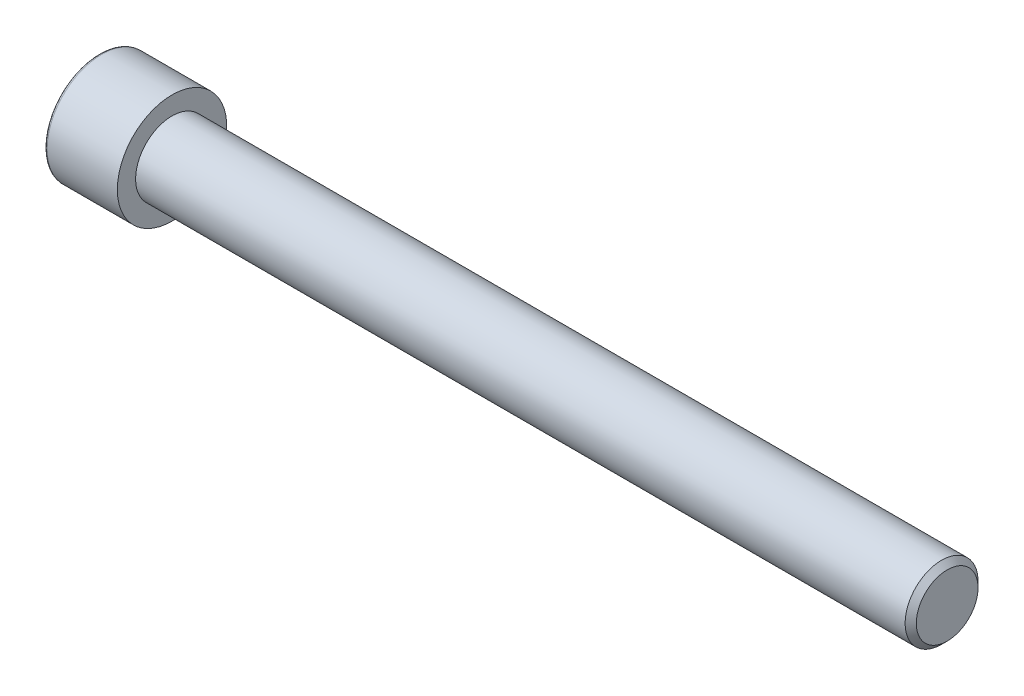
SolidWorks part; units mm, degrees
ref_plane "Płaszczyzna przednia" through (0, 0, 0) normal (0, 0, 1) x (1, 0, 0)
ref_plane "Płaszczyzna górna" through (0, 0, 0) normal (0, 1, 0) x (1, 0, 0)
ref_plane "Płaszczyzna prawa" through (0, 0, 0) normal (1, 0, 0) x (0, 0, -1)
sketch "Szkic1" plane through (0, 0, 0) normal (0, 0, 1) x (1, 0, 0)
  line L0 (0, 0) -> (0, 12)
  line L1 (0, 12) -> (16, 12)
  line L2 (16, 12) -> (16, 0)
  line L3 (16, 0) -> (0, 0)
  line L4 (16, 0) -> (0, 0) construction
revolve "Obrót1" add sketch "Szkic1" angle 360 about L4 reverse direction yes
sketch "Szkic2" plane through (0, 0, 0) normal (0, 0, 1) x (1, 0, 0)
  line L0 (0, 12) -> (0, 11.4)
  line L1 (0.6, 12) -> (0, 12)
  line L2 (16, 0) -> (0, 0) construction
  arc A0 (0, 11.4) -> (0.6, 12) centre (0.6, 11.4) cw
revolve "Wycięcie-obrót1" cut sketch "Szkic2" angle 360 about L2 reverse direction yes
sketch "Szkic3" plane through (0, 0, 0) normal (0, 0, 1) x (1, 0, 0)
  line L0 (16, 0) -> (16, 8)
  line L1 (16, 8) -> (184.773, 8)
  line L2 (184.773, 8) -> (186, 6.773)
  line L3 (186, 6.773) -> (186, 0)
  line L4 (186, 0) -> (16, 0)
  line L5 (186, 0) -> (16, 0) construction
revolve "Obrót2" add sketch "Szkic3" angle 360 about L5 reverse direction yes
cosmetic thread "Oznaczenie gwintu1" parameters "D1"=44, "D2"=13.546
sketch "Szkic4" plane through (0, 0, 0) normal (0, 0, 1) x (1, 0, 0)
  line L0 (0, 0) -> (0, 8.5)
  line L1 (0, 8.5) -> (8, 8.5)
  line L2 (8, 8.5) -> (12.9075, 0)
  line L3 (12.9075, 0) -> (0, 0)
  line L4 (12.9075, 0) -> (0, 0) construction
revolve "Wycięcie-obrót2" cut sketch "Szkic4" angle 360 about L4 reverse direction yes
sketch "Szkic5" plane through (0, 0, 0) normal (1, 0, 0) x (0, 0, -1)
  line L0 (-7, 4.0415) -> (-7, -4.0415)
  line L1 (-7, -4.0415) -> (0, -8.0829)
  line L2 (0, -8.0829) -> (7, -4.0415)
  line L3 (7, -4.0415) -> (7, 4.0415)
  line L4 (7, 4.0415) -> (0, 8.0829)
  line L5 (0, 8.0829) -> (-7, 4.0415)
  circle A0 centre (0, 0) radius 9
extrude "Dodanie-wyciągnięcie1" add sketch "Szkic5" along normal blind 12
ref_plane "Płaszczyzna1" through (16, 0, 0) normal (1, 0, 0) x (0, 0, -1)
ref_plane "IP2 XY" through (16, 0, 0) normal (-1, 0, 0) x (0, 0, 1)
ref_plane "IP2 XZ" through (0, 0, 0) normal (0, 1, 0) x (1, 0, 0)
ref_plane "IP2 YZ" through (0, 0, 0) normal (0, 0, -1) x (-1, 0, 0)
ref_axis "IP2 X" through (16, 0, 80.9) along (0, 0, -1)
ref_axis "IP2 Y" through (16, 50, 0) along (0, -1, 0)
ref_axis "IP2 Z" through (-80.9, 0, 0) along (1, 0, 0)
sketch3d "IP2"
  point P0 (16, 0, 0)
